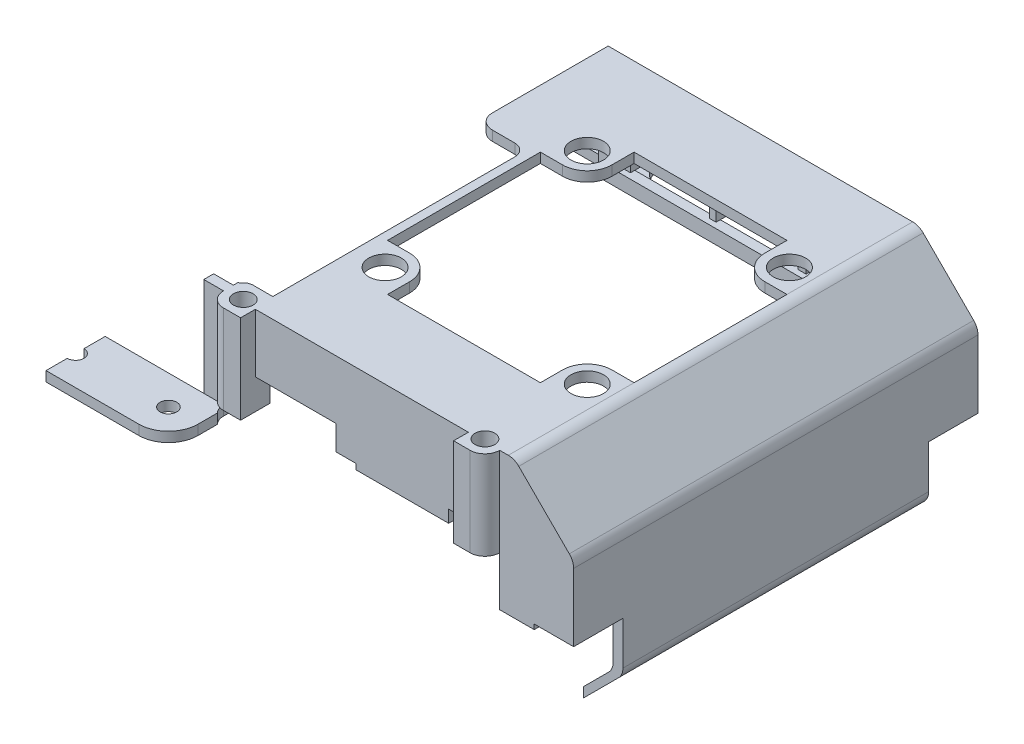
SolidWorks part; units mm, degrees
ref_plane "前视基准面" through (0, 0, 0) normal (0, 0, 1) x (1, 0, 0)
ref_plane "上视基准面" through (0, 0, 0) normal (0, 1, 0) x (1, 0, 0)
ref_plane "右视基准面" through (0, 0, 0) normal (1, 0, 0) x (0, 0, -1)
sketch "草图1" plane through (0, 0, 0) normal (0, 0, 1) x (1, 0, 0)
  line L0 (0, 0) -> (0, 2)
  line L1 (0, 2) -> (3, 2)
  line L5 (-60, 49) -> (3, 49)
  line L7 (0, 0) -> (3, 0)
  line L13 (3, 47) -> (-60, 47)
  line L15 (3, 2) -> (13, 12)
  line L16 (3, 0) -> (15, 12)
  line L17 (13, 37) -> (13, 12)
  line L18 (15, 12) -> (15, 37)
  line L19 (3, 47) -> (13, 37)
  line L20 (3, 49) -> (15, 37)
  line L21 (-60, 49) -> (-60, 47)
extrude "凸台-拉伸1" add sketch "草图1" along normal blind 82
fillet "圆角1" radius 3 8 edges at (3, 0, 41) (15, 12, 41) (15, 37, 41) (3, 49, 41) (3, 2, 41) (13, 12, 41) (13, 37, 41) (3, 47, 41)
sketch "草图4" plane through (0, 0, 0) normal (0, 0, -1) x (-1, 0, 0)
  line L0 (0, 0) -> (0, 26)
  line L1 (0, 26) -> (4, 26)
  line L2 (4, 26) -> (4, 27)
  line L3 (4, 27) -> (60, 27)
  line L4 (60, 27) -> (60, 49)
  line L5 (60, 49) -> (-1.7574, 49)
  line L6 (-1.7574, 49) -> (60, 49) construction
  line L7 (-3.8787, 48.1213) -> (-14.1213, 37.8787)
  line L8 (-15, 35.7574) -> (-15, 13.2426)
  line L9 (-14.1213, 11.1213) -> (-3.8787, 0.8787)
  line L10 (-1.7574, 0) -> (0, 0)
  arc A0 (-1.7574, 49) -> (-3.8787, 48.1213) centre (-1.7574, 46) ccw construction
  arc A1 (-1.7574, 49) -> (-3.8787, 48.1213) centre (-1.7574, 46) ccw
  arc A2 (-14.1213, 37.8787) -> (-15, 35.7574) centre (-12, 35.7574) ccw
  arc A3 (-15, 13.2426) -> (-14.1213, 11.1213) centre (-12, 13.2426) ccw
  arc A4 (-3.8787, 0.8787) -> (-1.7574, 0) centre (-1.7574, 3) ccw
extrude "凸台-拉伸2" add sketch "草图4" against normal blind 2
extrude "凸台-拉伸3" add sketch "草图4<2>" along normal blind 2 from offset 82 offset against normal yes
sketch "草图4<2>" plane through (0, 0, 0) normal (0, 0, -1) x (-1, 0, 0) same geometry as "草图4"
sketch "草图5" plane through (0, 0, 0) normal (0, 0, -1) x (-1, 0, 0)
  line L0 (2.6616, 45.0208) -> (2.6616, 31)
  line L1 (2.6616, 31) -> (0, 31)
  line L2 (0, 31) -> (0, 29.8631)
  line L3 (0, 29.8631) -> (56, 29.8631)
  line L4 (56, 29.8631) -> (56, 31)
  line L5 (56, 31) -> (53.4695, 31)
  line L6 (53.4695, 31) -> (53.4695, 44.3)
  line L7 (53.4695, 44.3) -> (37.4695, 44.3)
  line L8 (37.4695, 44.3) -> (37.4695, 31)
  line L9 (37.4695, 31) -> (36.113, 31)
  line L10 (36.113, 31) -> (36.113, 38.112)
  line L11 (36.113, 38.112) -> (19.513, 38.112)
  line L12 (19.513, 38.112) -> (19.513, 31)
  line L13 (19.513, 31) -> (17.8616, 31)
  line L14 (17.8616, 31) -> (17.8616, 45.0208)
  line L15 (17.8616, 45.0208) -> (2.6616, 45.0208)
extrude "切除-拉伸1" cut sketch "草图5" against normal blind 2
sketch "草图6" plane through (0, 0, 82) normal (0, 0, 1) x (1, 0, 0)
  line L13 (-56, 31) -> (-49.5434, 31)
  line L14 (-49.5434, 31) -> (-49.5434, 37.1214)
  line L15 (-49.5434, 37.1214) -> (-33.1434, 37.1214)
  line L16 (-33.1434, 37.1214) -> (-33.1434, 32.1214)
  line L17 (-33.1434, 37.1214) -> (-33.1434, 31) construction
  line L18 (-33.1434, 32.1214) -> (-29.1434, 32.1214)
  line L19 (-29.1434, 32.1214) -> (-29.1434, 31)
  line L20 (-3, 31) -> (-33.1434, 31) construction
  line L21 (-29.1434, 31) -> (-10.3442, 31)
  line L22 (-10.3442, 31) -> (-10.3442, 33.5)
  line L23 (-10.3442, 33.5) -> (-6.3442, 33.5)
  line L24 (-6.3442, 33.5) -> (-6.3442, 31)
  line L25 (-6.3442, 31) -> (0, 31)
  line L26 (-56, 31) -> (-56, 27)
  line L27 (-4, 27) -> (-60, 27) construction
  line L29 (0, 27) -> (0, 31)
  line L30 (0, 27) -> (0, 26)
  line L31 (0, 26) -> (-4, 26)
  line L32 (-4, 26) -> (-4, 27)
  line L33 (-4, 27) -> (-56, 27)
extrude "切除-拉伸2" cut sketch "草图6" against normal blind 2
sketch "草图7" plane through (0, 49, 0) normal (0, 1, 0) x (1, 0, 0)
  line L0 (-50, -66) -> (-50, -78)
  line L6 (-50, -66) -> (-50, -41)
  line L9 (-60, -82) -> (-60, 0) construction
  line L16 (-57, -26.4948) -> (-52.4369, -26.4948)
  line L17 (-60, -23.4948) -> (-60, -80)
  line L18 (-50, -41) -> (-50, -28.9317)
  line L21 (-38.7426, -20.5) -> (-38.7426, -16)
  line L24 (-43.7426, -25.5) -> (-48.2426, -25.5)
  line L26 (-60, -80) -> (-56, -80)
  line L27 (-7.7426, -16) -> (-38.7426, -16)
  line L28 (1.7574, -80) -> (-60, -80) construction
  line L29 (-54, -78) -> (-50, -78)
  line L30 (-48.2426, -56.5) -> (-48.2426, -25.5)
  line L31 (-2.7426, -56.5) -> (1.7574, -56.5)
  line L33 (-7.7426, -20.5) -> (-7.7426, -16)
  line L34 (-2.7426, -25.5) -> (1.7574, -25.5)
  line L35 (1.7574, -56.5) -> (1.7574, -25.5)
  line L36 (-7.7426, -61.5) -> (-7.7426, -66)
  line L37 (-7.7426, -66) -> (-38.7426, -66)
  line L38 (-43.7426, -56.5) -> (-48.2426, -56.5)
  line L39 (-38.7426, -61.5) -> (-38.7426, -66)
  circle A2 centre (-52.4948, -81.4948) radius 2
  circle A5 centre (-3.4982, -81.4948) radius 2
  arc A7 (-52.4369, -26.4948) -> (-50, -28.9317) centre (-52.4369, -28.9317) cw
  arc A8 (-60, -23.4948) -> (-57, -26.4948) centre (-57, -23.4948) ccw
  arc A10 (-56, -80) -> (-54, -78) centre (-54, -80) cw
  circle A11 centre (-43.7426, -20.5) radius 3.3
  arc A15 (-43.7426, -25.5) -> (-38.7426, -20.5) centre (-43.7426, -20.5) ccw
  circle A16 centre (-2.7426, -20.5) radius 3.3
  arc A17 (-2.7426, -25.5) -> (-7.7426, -20.5) centre (-2.7426, -20.5) cw
  arc A18 (-2.7426, -56.5) -> (-7.7426, -61.5) centre (-2.7426, -61.5) ccw
  circle A19 centre (-2.7426, -61.5) radius 3.3
  arc A20 (-43.7426, -56.5) -> (-38.7426, -61.5) centre (-43.7426, -61.5) cw
  circle A21 centre (-43.7426, -61.5) radius 3.3
extrude "切除-拉伸3" cut sketch "草图7" against normal up to next
sketch "草图8" plane through (0, 49, 0) normal (0, 1, 0) x (1, 0, 0)
  line L1 (-6.3442, -79) -> (0, -79)
  line L2 (0, -79) -> (0, -82)
  line L6 (-6.3442, -82) -> (-6.3442, -85)
  line L7 (-3, -85) -> (-33.1434, -85) construction
  line L8 (-6.3442, -85) -> (-3, -85)
  line L9 (-49.5434, -82) -> (-49.5434, -79)
  line L10 (-49.5434, -86.4622) -> (-49.5434, -73.9622) construction
  line L13 (-56, -79) -> (-49.5434, -79)
  line L15 (-53, -85) -> (-49.5434, -85)
  line L16 (-49.5434, -85) -> (-49.5434, -82)
  line L17 (-54.4299, -82) -> (-60, -82) construction
  line L18 (-56, -79) -> (-56, -82)
  line L19 (-6.3442, -79) -> (-6.3442, -82)
  circle A0 centre (-52.4948, -81.4948) radius 2
  circle A2 centre (-3.4982, -81.4948) radius 2
  arc A3 (0, -82) -> (-3, -85) centre (-3, -82) cw
  arc A5 (-53, -85) -> (-56, -82) centre (-53, -82) cw
extrude "凸台-拉伸4" add sketch "草图8" against normal blind 18
sketch "草图9" plane through (0, 0, 0) normal (-1, 0, 0) x (0, 0, 1)
  line L2 (1, 1) -> (8, 1)
  line L3 (8, 1) -> (8, 21)
  line L4 (8, 21) -> (1, 21)
  line L5 (1, 21) -> (1, 1)
  line L6 (81, 21) -> (81, 1)
  line L7 (74, 21) -> (81, 21)
  line L8 (74, 1) -> (74, 21)
  line L9 (81, 1) -> (74, 1)
extrude "凸台-拉伸5" add sketch "草图9" against normal blind 2
sketch "草图10" plane through (0, 0, 0) normal (-1, 0, 0) x (0, 0, 1)
  line L0 (8, 21) -> (6, 21)
  line L1 (8, 21) -> (2, 21) construction
  line L2 (6, 21) -> (6, 1)
  line L3 (6, 1) -> (8, 1)
  line L4 (8, 1) -> (8, 21)
  line L7 (74, 1) -> (74, 21)
  line L8 (76, 1) -> (74, 1)
  line L9 (76, 21) -> (76, 1)
  line L10 (74, 21) -> (76, 21)
extrude "凸台-拉伸6" add sketch "草图10" along normal blind 1
sketch "草图11" plane through (-1, 0, 0) normal (-1, 0, 0) x (0, 0, 1)
  line L0 (8, 21) -> (1, 21)
  line L1 (1, 21) -> (1, 1)
  line L2 (1, 1) -> (8, 1)
  line L3 (8, 1) -> (8, 21)
  line L6 (74, 1) -> (74, 21)
  line L7 (81, 1) -> (74, 1)
  line L8 (81, 21) -> (81, 1)
  line L9 (74, 21) -> (81, 21)
extrude "凸台-拉伸7" add sketch "草图11" along normal blind 2
sketch "草图12" plane through (15, 0, 0) normal (1, 0, 0) x (0, 0, -1)
  line L0 (-82, 0) -> (-72, 0)
  line L1 (0, 0) -> (-82, 0) construction
  line L2 (-72, 0) -> (-72, 22)
  line L3 (-72, 22) -> (-82, 22)
  line L4 (-82, 13.2426) -> (-82, 35.7574) construction
  line L5 (-82, 22) -> (-82, 0)
  line L7 (0, 22) -> (0, 0)
  line L8 (-10, 22) -> (0, 22)
  line L9 (-10, 0) -> (-10, 22)
  line L10 (0, 0) -> (-10, 0)
extrude "切除-拉伸4" cut sketch "草图12" against normal blind 8
sketch "草图13" plane through (0, 0, 0) normal (0, -1, 0) x (1, 0, 0)
  line L0 (0, 0) -> (-4, 0) construction
  line L1 (7, 82) -> (-3, 82)
  line L2 (7, 82) -> (7, 0)
  line L3 (7, 0) -> (-3, 0)
  line L4 (-3, 82) -> (-3, 0)
extrude "切除-拉伸5" cut sketch "草图13" against normal blind 21
sketch "草图14" plane through (0, 27, 0) normal (0, -1, 0) x (1, 0, 0)
  line L1 (-4, 0) -> (-60, 0) construction
  line L2 (-55.1739, 0) -> (-80, 0)
  line L3 (-80, 0) -> (-80, -4.3)
  line L4 (-55.1739, 0) -> (-49.1739, 0)
  line L5 (-80, -7.7) -> (-80, -12)
  line L6 (-80, -12) -> (-61.1739, -12)
  line L8 (-80, 94) -> (-61.1739, 94)
  line L9 (-80, 89.7) -> (-80, 94)
  line L11 (-80, 82) -> (-80, 86.3)
  line L13 (-55.1739, 84.0674) -> (-55.1739, 88)
  line L14 (-80, 82) -> (-56, 82)
  circle A0 centre (-61.1739, -6) radius 1.7
  arc A1 (-61.1739, -12) -> (-55.1739, -6) centre (-61.1739, -6) ccw
  arc A2 (-61.1739, -12) -> (-55.1739, -6) centre (-61.1739, -6) ccw construction
  arc A3 (-80, -7.7) -> (-80, -4.3) centre (-80, -6) ccw
  arc A4 (-55.1739, -6) -> (-49.1739, 0) centre (-49.1739, -6) cw
  arc A6 (-80, 89.7) -> (-80, 86.3) centre (-80, 88) cw
  arc A7 (-61.1739, 94) -> (-55.1739, 88) centre (-61.1739, 88) cw
  circle A8 centre (-61.1739, 88) radius 1.7
  arc A9 (-56, 82) -> (-55.1739, 84.0674) centre (-53, 82) cw
extrude "凸台-拉伸8" add sketch "草图14" against normal blind 2
